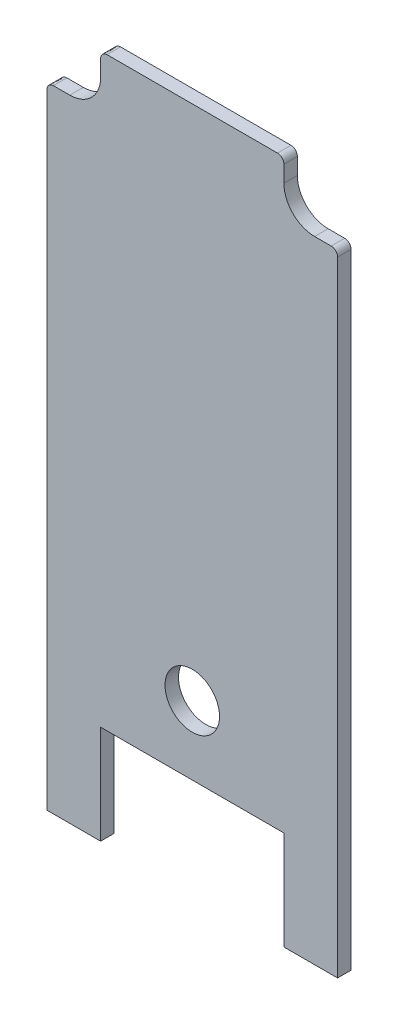
SolidWorks part; units mm, degrees
ref_plane "Front Plane" through (0, 0, 0) normal (0, 0, 1) x (1, 0, 0)
ref_plane "Top Plane" through (0, 0, 0) normal (0, 1, 0) x (1, 0, 0)
ref_plane "Right Plane" through (0, 0, 0) normal (1, 0, 0) x (0, 0, -1)
sketch3d "3DSketch1" plane through (0, 0, 0) normal (0, 0, 1) x (1, 0, 0)
  dimension "D1" = 5
sketch "Sketch2" plane through (0, 0, 5) normal (0, 0, 1) x (1, 0, 0)
  line L0 (-18.9245, -40.3) -> (-18.9245, 40.3)
  line L1 (13.25, -45.9745) -> (-13.25, -45.9745)
  line L2 (-13.25, 45.9745) -> (13.25, 45.9745)
  line L3 (18.9245, 40.3) -> (18.9245, -40.3)
  line L4 (-16.1749, 37.9745) -> (-14.25, 37.9745)
  line L5 (10.9245, 43.2249) -> (10.9245, 41.3)
  line L6 (17.1745, 36.9749) -> (17.1745, -37.0249)
  line L7 (14.25, 37.9745) -> (16.1749, 37.9745)
  line L8 (-9.9249, 44.2245) -> (9.9249, 44.2245)
  line L9 (-10.9245, 41.3) -> (-10.9245, 43.2249)
  line L10 (-17.1745, -36.9249) -> (-17.1745, 36.9749)
  line L11 (-14.25, -37.9245) -> (-16.1749, -37.9245)
  line L12 (-10.8745, -43.2249) -> (-10.8745, -41.3)
  line L13 (9.9749, -44.2245) -> (-9.8749, -44.2245)
  line L14 (10.9745, -41.3) -> (10.9745, -43.2249)
  line L15 (16.1749, -38.0245) -> (14.25, -38.0245)
  line L16 (16.1749, -38.0245) -> (14.25, -38.0245) construction
  line L17 (10.9745, -41.3) -> (10.9745, -43.2249) construction
  line L18 (9.9749, -44.2245) -> (-9.8749, -44.2245) construction
  line L19 (-10.8745, -43.2249) -> (-10.8745, -41.3) construction
  line L20 (-14.25, -37.9245) -> (-16.1749, -37.9245) construction
  line L21 (-17.1745, -36.9249) -> (-17.1745, 36.9749) construction
  line L22 (-10.9245, 41.3) -> (-10.9245, 43.2249) construction
  line L23 (-9.9249, 44.2245) -> (9.9249, 44.2245) construction
  line L24 (14.25, 37.9745) -> (16.1749, 37.9745) construction
  line L25 (17.1745, 36.9749) -> (17.1745, -37.0249) construction
  line L26 (10.9245, 43.2249) -> (10.9245, 41.3) construction
  line L27 (-16.1749, 37.9745) -> (-14.25, 37.9745) construction
  line L28 (18.9245, 40.3) -> (18.9245, -40.3) construction
  line L29 (-13.25, 45.9745) -> (13.25, 45.9745) construction
  line L30 (13.25, -45.9745) -> (-13.25, -45.9745) construction
  line L31 (-18.9245, -40.3) -> (-18.9245, 40.3) construction
  line L32 (-16.9205, -24.2245) -> (-16.9205, 36.9749)
  line L33 (-16.1749, 37.7205) -> (-14.25, 37.7205)
  line L34 (-10.6705, 41.3) -> (-10.6705, 43.2249)
  line L35 (-9.9249, 43.9705) -> (9.9249, 43.9705)
  line L36 (10.6705, 43.2249) -> (10.6705, 41.3)
  line L37 (14.25, 37.7205) -> (16.1749, 37.7205)
  line L38 (16.9205, 36.9749) -> (16.9205, -35.7245)
  line L44 (-10.6705, -24.2245) -> (10.6705, -24.2245)
  line L45 (-16.9205, -36.8196) -> (-16.9205, 36.9749) construction
  line L46 (16.9205, 36.9749) -> (16.9205, -36.9196) construction
  line L47 (17.1745, -37.0249) -> (16.1749, -38.0245) construction
  line L48 (16.9205, -36.9196) -> (16.0696, -37.7705) construction
  line L49 (10.9745, -43.2249) -> (9.9749, -44.2245) construction
  line L50 (10.7205, -43.1196) -> (9.8696, -43.9705) construction
  line L51 (-9.8749, -44.2245) -> (-10.8745, -43.2249) construction
  line L52 (-9.7696, -43.9705) -> (-10.6205, -43.1196) construction
  line L53 (-16.1749, -37.9245) -> (-17.1745, -36.9249) construction
  line L54 (-16.0696, -37.6705) -> (-16.9205, -36.8196) construction
  line L55 (0, -45.9745) -> (0, 45.9745) construction
  line L56 (-16.9205, -24.2245) -> (-10.6705, -24.2245)
  line L57 (-16.9205, -24.2245) -> (-16.9205, -35.7245)
  line L58 (-16.9205, -35.7245) -> (-10.6705, -35.7245)
  line L59 (-10.6705, -24.2245) -> (-10.6705, -35.7245)
  line L60 (16.0696, -37.7705) -> (14.25, -37.7705) construction
  line L61 (10.7205, -41.3) -> (10.7205, -43.1196) construction
  line L62 (9.8696, -43.9705) -> (-9.7696, -43.9705) construction
  line L63 (-10.6205, -43.1196) -> (-10.6205, -41.3) construction
  line L64 (-14.25, -37.6705) -> (-16.0696, -37.6705) construction
  line L65 (10.6705, -24.2245) -> (10.6705, -35.7245)
  line L66 (16.9205, -35.7245) -> (10.6705, -35.7245)
  arc A0 (-18.9245, -40.3) -> (-13.25, -45.9745) centre (-13.25, -40.3) ccw
  arc A1 (-13.25, 45.9745) -> (-18.9245, 40.3) centre (-13.25, 40.3) ccw
  arc A2 (18.9245, 40.3) -> (13.25, 45.9745) centre (13.25, 40.3) ccw
  arc A3 (13.25, -45.9745) -> (18.9245, -40.3) centre (13.25, -40.3) ccw
  arc A4 (-14.25, 37.9745) -> (-10.9245, 41.3) centre (-14.25, 41.3) ccw
  arc A5 (10.9245, 41.3) -> (14.25, 37.9745) centre (14.25, 41.3) ccw
  circle A6 centre (14.25, -41.3) radius 1.321
  circle A7 centre (-14.25, 41.3) radius 1.321
  circle A8 centre (-14.25, -41.3) radius 1.321
  circle A9 centre (14.25, 41.3) radius 1.321
  arc A10 (-10.8745, -41.3) -> (-14.25, -37.9245) centre (-14.25, -41.3) ccw
  arc A11 (14.25, -38.0245) -> (10.9745, -41.3) centre (14.25, -41.3) ccw
  arc A12 (14.25, -38.0245) -> (10.9745, -41.3) centre (14.25, -41.3) ccw construction
  arc A13 (-10.8745, -41.3) -> (-14.25, -37.9245) centre (-14.25, -41.3) ccw construction
  circle A14 centre (14.25, 41.3) radius 1.321 construction
  circle A15 centre (-14.25, -41.3) radius 1.321 construction
  circle A16 centre (-14.25, 41.3) radius 1.321 construction
  circle A17 centre (14.25, -41.3) radius 1.321 construction
  arc A18 (10.9245, 41.3) -> (14.25, 37.9745) centre (14.25, 41.3) ccw construction
  arc A19 (-14.25, 37.9745) -> (-10.9245, 41.3) centre (-14.25, 41.3) ccw construction
  arc A20 (13.25, -45.9745) -> (18.9245, -40.3) centre (13.25, -40.3) ccw construction
  arc A21 (18.9245, 40.3) -> (13.25, 45.9745) centre (13.25, 40.3) ccw construction
  arc A22 (-13.25, 45.9745) -> (-18.9245, 40.3) centre (-13.25, 40.3) ccw construction
  arc A23 (-18.9245, -40.3) -> (-13.25, -45.9745) centre (-13.25, -40.3) ccw construction
  arc A24 (-14.25, 37.7205) -> (-10.6705, 41.3) centre (-14.25, 41.3) ccw
  arc A25 (10.6705, 41.3) -> (14.25, 37.7205) centre (14.25, 41.3) ccw
  circle A28 centre (0, -16.2245) radius 3.175
  arc A40 (14.25, -37.7705) -> (10.7205, -41.3) centre (14.25, -41.3) ccw construction
  arc A41 (-10.6205, -41.3) -> (-14.25, -37.6705) centre (-14.25, -41.3) ccw construction
  spline S0 degree 3 poles (16.1749, 37.9745) (16.7605, 37.9745) (17.1745, 37.5605) (17.1745, 36.9749) knots 0 0 0 0 1 1 1 1 weights 1 0.804899 0.804899 1
  spline S1 degree 3 poles (9.9249, 44.2245) (10.5105, 44.2245) (10.9245, 43.8105) (10.9245, 43.2249) knots 0 0 0 0 1 1 1 1 weights 1 0.804899 0.804899 1
  spline S2 degree 3 poles (-10.9245, 43.2249) (-10.9245, 43.8105) (-10.5105, 44.2245) (-9.9249, 44.2245) knots 0 0 0 0 1 1 1 1 weights 1 0.804899 0.804899 1
  spline S3 degree 3 poles (-17.1745, 36.9749) (-17.1745, 37.5605) (-16.7605, 37.9745) (-16.1749, 37.9745) knots 0 0 0 0 1 1 1 1 weights 1 0.804899 0.804899 1
  spline S4 degree 3 poles (-16.1749, -37.9245) (-16.7605, -37.9245) (-17.1745, -37.5105) (-17.1745, -36.9249) knots 0 0 0 0 1 1 1 1 weights 1 0.804899 0.804899 1
  spline S5 degree 3 poles (-9.8749, -44.2245) (-10.4605, -44.2245) (-10.8745, -43.8105) (-10.8745, -43.2249) knots 0 0 0 0 1 1 1 1 weights 1 0.804899 0.804899 1
  spline S6 degree 3 poles (10.9745, -43.2249) (10.9745, -43.8105) (10.5605, -44.2245) (9.9749, -44.2245) knots 0 0 0 0 1 1 1 1 weights 1 0.804899 0.804899 1
  spline S7 degree 3 poles (17.1745, -37.0249) (17.1745, -37.6105) (16.7605, -38.0245) (16.1749, -38.0245) knots 0 0 0 0 1 1 1 1 weights 1 0.804899 0.804899 1
  spline S8 degree 3 poles (17.1745, -37.0249) (17.1745, -37.6105) (16.7605, -38.0245) (16.1749, -38.0245) knots 0 0 0 0 1 1 1 1 weights 1 0.804899 0.804899 1 construction
  spline S9 degree 3 poles (10.9745, -43.2249) (10.9745, -43.8105) (10.5605, -44.2245) (9.9749, -44.2245) knots 0 0 0 0 1 1 1 1 weights 1 0.804899 0.804899 1 construction
  spline S10 degree 3 poles (-9.8749, -44.2245) (-10.4605, -44.2245) (-10.8745, -43.8105) (-10.8745, -43.2249) knots 0 0 0 0 1 1 1 1 weights 1 0.804899 0.804899 1 construction
  spline S11 degree 3 poles (-16.1749, -37.9245) (-16.7605, -37.9245) (-17.1745, -37.5105) (-17.1745, -36.9249) knots 0 0 0 0 1 1 1 1 weights 1 0.804899 0.804899 1 construction
  spline S12 degree 3 poles (-17.1745, 36.9749) (-17.1745, 37.5605) (-16.7605, 37.9745) (-16.1749, 37.9745) knots 0 0 0 0 1 1 1 1 weights 1 0.804899 0.804899 1 construction
  spline S13 degree 3 poles (-10.9245, 43.2249) (-10.9245, 43.8105) (-10.5105, 44.2245) (-9.9249, 44.2245) knots 0 0 0 0 1 1 1 1 weights 1 0.804899 0.804899 1 construction
  spline S14 degree 3 poles (9.9249, 44.2245) (10.5105, 44.2245) (10.9245, 43.8105) (10.9245, 43.2249) knots 0 0 0 0 1 1 1 1 weights 1 0.804899 0.804899 1 construction
  spline S15 degree 3 poles (16.1749, 37.9745) (16.7605, 37.9745) (17.1745, 37.5605) (17.1745, 36.9749) knots 0 0 0 0 1 1 1 1 weights 1 0.804899 0.804899 1 construction
  spline S16 degree 1 poles (-16.9205, 36.9749) (-16.1749, 37.7205) knots 0 0 1 1 construction
  spline S17 degree 1 poles (-10.6705, 43.2249) (-9.9249, 43.9705) knots 0 0 1 1 construction
  spline S18 degree 1 poles (9.9249, 43.9705) (10.6705, 43.2249) knots 0 0 1 1 construction
  spline S19 degree 1 poles (16.1749, 37.7205) (16.9205, 36.9749) knots 0 0 1 1 construction
  spline S24 degree 3 poles (-16.9205, 36.9749) (-16.9205, 37.068) (-16.8885, 37.2502) (-16.7186, 37.5186) (-16.4502, 37.6885) (-16.268, 37.7205) (-16.1749, 37.7205) knots 0 0 0 0 0.25 0.5 0.75 1 1 1 1
  spline S25 degree 3 poles (-10.6705, 43.2249) (-10.6705, 43.318) (-10.6385, 43.5002) (-10.4686, 43.7686) (-10.2002, 43.9385) (-10.018, 43.9705) (-9.9249, 43.9705) knots 0 0 0 0 0.25 0.5 0.75 1 1 1 1
  spline S26 degree 3 poles (9.9249, 43.9705) (10.018, 43.9705) (10.2002, 43.9385) (10.4686, 43.7686) (10.6385, 43.5002) (10.6705, 43.318) (10.6705, 43.2249) knots 0 0 0 0 0.25 0.5 0.75 1 1 1 1
  spline S27 degree 3 poles (16.1749, 37.7205) (16.268, 37.7205) (16.4502, 37.6885) (16.7186, 37.5186) (16.8885, 37.2502) (16.9205, 37.068) (16.9205, 36.9749) knots 0 0 0 0 0.25 0.5 0.75 1 1 1 1
  point P92 (16.9205, -24.8615)
  point P93 (10.6053, -24.2245)
  point P94 (0, 0)
  point P95 (16.9205, -24.9883)
  point P96 (16.9205, -24.2245)
  point P97 (0, 0)
  point P98 (16.9205, -35.8921)
  dimension "D5" = 6.35
  dimension "D2" = 20
  dimension "D3" = 11.5
  dimension "D4" = 6.25
  dimension "D6" = 8
  dimension "D1" = 0.254
extrude "Boss-Extrude1" add sketch "Sketch2" along normal blind 1.57 contours S27 L37 A25 L36 S26 L35 S25 L34 A24 L33 S24 L32 L44 L38 A28 | L57 L56 L59 L58 region at (0.4359, 7.9764, 5)
